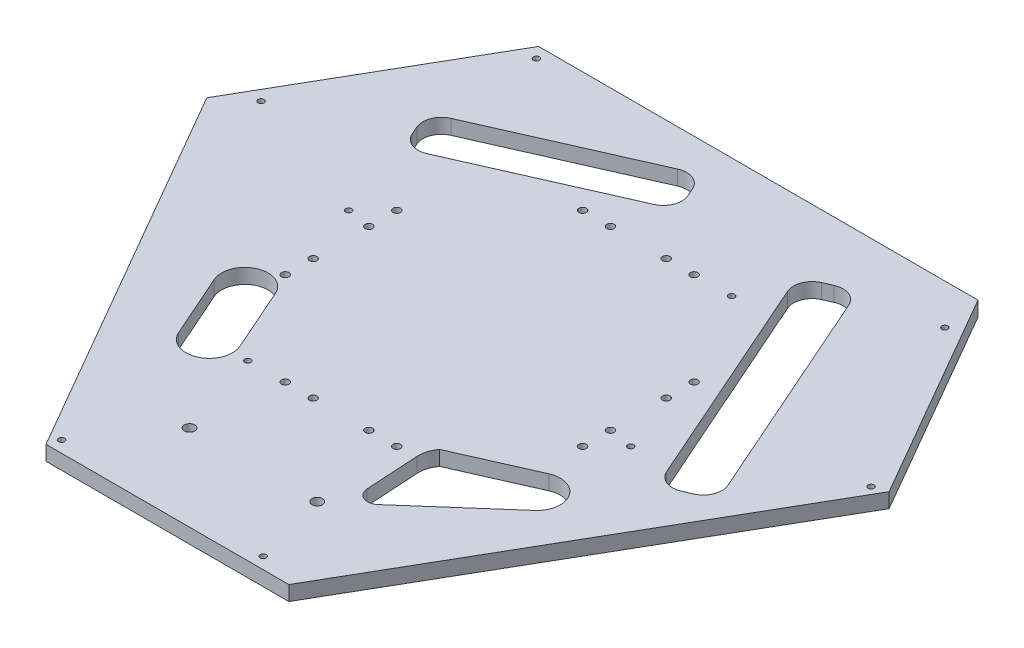
SolidWorks part; units mm, degrees
material "Pin"
ref_plane "Plan de face" through (0, 0, 0) normal (0, 0, 1) x (1, 0, 0)
ref_plane "Plan de dessus" through (0, 0, 0) normal (0, 1, 0) x (1, 0, 0)
ref_plane "Plan de droite" through (0, 0, 0) normal (1, 0, 0) x (0, 0, -1)
sketch "BB_position" plane through (0, 0, 0) normal (0, 1, 0) x (1, 0, 0)
  line L0 (-112.5, 64.9519) -> (112.5, 64.9519) construction
  line L7 (112.5, 64.9519) -> (0, -129.9038) construction
  line L8 (0, -129.9038) -> (-112.5, 64.9519) construction
  circle A0 centre (0, 0) radius 129.9038 construction
  circle A1 centre (-112.5, 64.9519) radius 5 construction
  circle A2 centre (112.5, 64.9519) radius 5 construction
  circle A3 centre (0, -129.9038) radius 5 construction
  dimension "D1" = 225
  dimension "D2" = 10
sketch "BB_Footprint" plane through (0, 0, 0) normal (0, 1, 0) x (1, 0, 0)
  line L0 (-112.5, 64.9519) -> (-130.615, 33.5758) construction
  line L1 (-130.615, 33.5758) -> (-133.9232, 35.4858) construction
  line L2 (-133.9232, 35.4858) -> (-90.5354, 110.6358) construction
  line L3 (97.6932, 98.238) -> (141.0811, 23.088) construction
  line L4 (112.5, 64.9519) -> (94.385, 96.328) construction
  line L5 (94.385, 96.328) -> (97.6932, 98.238) construction
  line L6 (36.23, -133.7238) -> (-50.5457, -133.7238) construction
  line L7 (0, -129.9038) -> (36.23, -129.9038) construction
  line L8 (36.23, -129.9038) -> (36.23, -133.7238) construction
  circle A0 centre (-112.5, 64.9519) radius 5 construction
  circle A1 centre (0, 0) radius 129.9038 construction
  circle A2 centre (-112.5, 64.9519) radius 5 construction
  circle A3 centre (112.5, 64.9519) radius 5 construction
  circle A4 centre (0, -129.9038) radius 5 construction
  point P23 (0, 0)
  dimension "D1" = 3.82
  dimension "D2" = 36.23
  dimension "D3" = 86.7757
  dimension "D4" = 3
sketch "Esquisse3" plane through (0, 0, 0) normal (0, 1, 0) x (1, 0, 0)
  line L0 (-94.5768, 115.6358) -> (94.5768, 115.6358)
  line L1 (-94.5768, 115.6358) -> (-146.8546, 25.088)
  line L2 (-146.8546, 25.088) -> (-52.2778, -138.7238)
  line L3 (-52.2778, -138.7238) -> (52.2778, -138.7238)
  line L4 (52.2778, -138.7238) -> (146.8546, 25.088)
  line L5 (146.8546, 25.088) -> (94.5768, 115.6358)
  line L6 (-133.9232, 35.4858) -> (-90.5354, 110.6358) construction
  point P2 (0, 115.6358)
  point P7 (0, -138.7238)
  dimension "D1" = 5
  dimension "D2" = 4
  dimension "D3" = 5
sketch "TB_boltPattern" plane through (0, 0, 0) normal (0, 1, 0) x (1, 0, 0)
  line L0 (0, 143.3581) -> (0, -141.7362) construction
  line L1 (-23, 57.7) -> (-13, 57.7) construction
  line L2 (-23, 57.7) -> (-23, 43.7) construction
  line L3 (-23, 43.7) -> (-13, 43.7) construction
  line L4 (-13, 57.7) -> (-13, 43.7) construction
  line L5 (-57.7, 23) -> (-43.7, 23) construction
  line L6 (-57.7, 23) -> (-57.7, 13) construction
  line L7 (-57.7, 13) -> (-43.7, 13) construction
  line L8 (-43.7, 23) -> (-43.7, 13) construction
  line L9 (-204.4729, 0) -> (279.6048, 0) construction
  circle A0 centre (-24, 64) radius 1.6 construction
  circle A1 centre (-12, 64) radius 1.6 construction
  circle A2 centre (-64, 24) radius 1.6 construction
  circle A3 centre (-64, 12) radius 1.6 construction
  point P8 (-18, 57.7)
  dimension "D5" = 3.2
  dimension "D10" = 6.3
  dimension "D1" = 12
  dimension "D2" = 12
  dimension "D3" = 40
  dimension "D4" = 40
  dimension "D6" = 14
  dimension "D7" = 10
  dimension "D8" = 1
  dimension "D9" = 6.3
  dimension "D11" = 1
  dimension "D12" = 12
  dimension "D13" = 12
extrude "Plate" add sketch "Esquisse3" against normal blind 6.35
hole_wizard "BBCase_boltPattern" positions "Esquisse6" profile "Esquisse8" hole size "M3" standard "Ansi Metric"
sketch "Esquisse6" plane through (0, 0, 0) normal (0, 1, 0) x (1, 0, 0)
  point P0 (-90.5354, 110.6358)
  point P3 (-133.9232, 35.4858)
sketch "Esquisse8" plane through (-90.5354, 0, -110.6358) normal (1, 0, 0) x (0, 0, 1)
  line L0 (0, 0) -> (0, 7.1311)
  line L1 (0, 7.1311) -> (1.3, 6.35)
  line L2 (1.3, 6.35) -> (1.3, 0)
  line L5 (1.3, 0) -> (0, 0)
  line L10 (0, 7.1311) -> (-1.3, 6.35) construction
  line L11 (0, -6.35) -> (0, 107.95) construction
  dimension "Diamètre du perçage" = 2.6
  dimension "Profondeur du perçage" = 6.35
  dimension "Angle de pointe" = 118
ref_axis "Axe1" through (0, 0, 0) along (0, 1, 0)
pattern_circular "Répétition circulaire1" count 3 over 360 about axis through (0, 0, 0) along (0, 1, 0) of "BBCase_boltPattern"
hole_wizard "Dégagement M32" positions "Esquisse9" profile "Esquisse10" hole size "M3" standard "Ansi Metric"
sketch "Esquisse9" plane through (0, 0, 0) normal (0, 1, 0) x (1, 0, 0)
  point P0 (-24, 64)
  point P3 (-12, 64)
  point P6 (-64, 24)
  point P9 (-64, 12)
sketch "Esquisse10" plane through (-24, 0, -64) normal (1, 0, 0) x (0, 0, 1)
  line L0 (0, 0) -> (0, 7.3114)
  line L1 (0, 7.3114) -> (1.6, 6.35)
  line L2 (1.6, 6.35) -> (1.6, 0)
  line L5 (1.6, 0) -> (0, 0)
  line L10 (0, 7.3114) -> (-1.6, 6.35) construction
  line L11 (0, -6.35) -> (0, 107.95) construction
  dimension "Diamètre du perçage" = 3.2
  dimension "Profondeur du perçage" = 6.35
  dimension "Angle de pointe" = 118
pattern_circular "Répétition circulaire2" count 4 over 360 about axis through (0, 0, 0) along (0, 1, 0) of "Dégagement M32"
sketch "HB_Footprint" plane through (0, 0, 0) normal (0, 1, 0) x (1, 0, 0)
  line L0 (-74.3426, 13.6262) -> (40.0015, 64.1278) construction
  line L1 (40.0015, 64.1278) -> (74.3426, -13.6262) construction
  line L2 (-74.3426, 13.6262) -> (-40.0015, -64.1278) construction
  line L3 (-40.0015, -64.1278) -> (74.3426, -13.6262) construction
  line L8 (-77.8072, 30.1336) -> (-30.1336, -77.8072) construction
  line L9 (-30.1336, -77.8072) -> (77.8072, -30.1336) construction
  line L10 (77.8072, -30.1336) -> (30.1336, 77.8072) construction
  line L11 (-77.8072, 30.1336) -> (30.1336, 77.8072) construction
  line L12 (-23.8368, 53.9704) -> (23.8368, -53.9704) construction
  line L13 (-57.1721, -25.2508) -> (0, 0) construction
  circle A0 centre (-74.3426, 13.6262) radius 1.6 construction
  circle A1 centre (40.0015, 64.1278) radius 1.6 construction
  circle A2 centre (-40.0015, -64.1278) radius 1.6 construction
  circle A3 centre (74.3426, -13.6262) radius 1.6 construction
  point P10 (23.8368, -53.9704)
  point P19 (-17.1706, 38.877)
  dimension "D4" = 3.2
  dimension "D1" = 125
  dimension "D2" = 85
  dimension "D3" = 118
hole_wizard "Dégagement M33" positions "Esquisse11" profile "Esquisse12" hole size "M3" standard "Ansi Metric"
sketch "Esquisse11" plane through (0, 0, 0) normal (0, 1, 0) x (1, 0, 0)
  point P0 (-74.3426, 13.6262)
  point P3 (-40.0015, -64.1278)
  point P6 (74.3426, -13.6262)
  point P9 (40.0015, 64.1278)
sketch "Esquisse12" plane through (-74.3426, 0, -13.6262) normal (1, 0, 0) x (0, 0, 1)
  line L0 (0, 0) -> (0, 7.1311)
  line L1 (0, 7.1311) -> (1.3, 6.35)
  line L2 (1.3, 6.35) -> (1.3, 0)
  line L5 (1.3, 0) -> (0, 0)
  line L10 (0, 7.1311) -> (-1.3, 6.35) construction
  line L11 (0, -6.35) -> (0, 107.95) construction
  dimension "Diamètre du perçage" = 2.6
  dimension "Profondeur du perçage" = 6.35
  dimension "Angle de pointe" = 118
sketch "Esquisse13" plane through (0, 0, 0) normal (0, 1, 0) x (1, 0, 0)
  line L0 (113.0252, -14.5791) -> (94.7302, -22.6594)
  line L1 (94.7302, -22.6594) -> (47.0566, 85.2815)
  line L2 (47.0566, 85.2815) -> (65.3516, 93.3617)
  line L3 (65.3516, 93.3617) -> (113.0252, -14.5791)
  line L5 (-77.8072, 30.1336) -> (30.1336, 77.8072) construction
  line L7 (40.0015, 64.1278) -> (74.3426, -13.6262) construction
  line L13 (-30.1336, -77.8072) -> (77.8072, -30.1336) construction
  line L14 (-11.64, 103.085) -> (-93.9678, 66.7238)
  line L15 (-93.9678, 66.7238) -> (-85.8875, 48.4287)
  line L16 (-85.8875, 48.4287) -> (-3.5597, 84.7899)
  line L17 (-3.5597, 84.7899) -> (-11.64, 103.085)
  line L18 (-77.8072, 30.1336) -> (-30.1336, -77.8072) construction
  dimension "D1" = 15
  dimension "D2" = 20
  dimension "D5" = 20
  dimension "D6" = 90
  dimension "D7" = 20
extrude "Enlèv. mat.-Extru.1" cut sketch "Esquisse13" against normal up to surface (6.35 mm away) up to face at (-40.0015, -6.35, 65.4278)
sketch "Esquisse15" plane through (0, 0, 0) normal (0, 1, 0) x (1, 0, 0)
  line L0 (-27.48, -101.7238) -> (27.48, -101.7238) construction
  line L1 (0, 200143.3581) -> (0, -200141.7362) construction
  line L2 (-52.2778, -138.7238) -> (52.2778, -138.7238) construction
  circle A0 centre (-27.48, -101.7238) radius 3.5746 construction
  circle A1 centre (27.48, -101.7238) radius 3.5746 construction
  point P4 (0, -101.7238)
  dimension "D1" = 54.96
  dimension "D2" = 37
hole_wizard "Dégagement M51" positions "Esquisse16" profile "Esquisse17" hole size "M5" standard "Ansi Metric"
sketch "Esquisse16" plane through (0, 0, 0) normal (0, 1, 0) x (1, 0, 0)
  point P0 (-27.48, -101.7238)
  point P3 (27.48, -101.7238)
sketch "Esquisse17" plane through (-27.48, 0, 101.7238) normal (1, 0, 0) x (0, 0, 1)
  line L0 (0, 0) -> (0, 7.714)
  line L1 (0, 7.714) -> (2.27, 6.35)
  line L2 (2.27, 6.35) -> (2.27, 0)
  line L5 (2.27, 0) -> (0, 0)
  line L10 (0, 7.714) -> (-2.27, 6.35) construction
  line L11 (0, -6.35) -> (0, 107.95) construction
  dimension "Diamètre du perçage" = 4.54
  dimension "Profondeur du perçage" = 6.35
  dimension "Angle de pointe" = 118
sketch "Esquisse18" plane through (0, 0, 0) normal (0, 1, 0) x (1, 0, 0)
  line L0 (71.0075, -50.6279) -> (43.5649, -62.7483) construction
  line L2 (66.9674, -41.4803) -> (34.336, -55.8925)
  line L3 (-30.1336, -77.8072) -> (77.8072, -30.1336) construction
  line L4 (23.8368, -53.9704) -> (77.8072, -30.1336) construction
  line L5 (50.822, -42.052) -> (57.2862, -56.6881) construction
  line L6 (-68.3683, -37.0282) -> (-56.2479, -64.4708) construction
  line L7 (-59.2207, -32.9881) -> (-47.1003, -60.4307)
  line L8 (-77.5158, -41.0684) -> (-65.3954, -68.511)
  line L9 (-74.3426, 13.6262) -> (-40.0015, -64.1278) construction
  line L10 (-57.1721, -25.2508) -> (-40.0015, -64.1278) construction
  line L11 (-48.5868, -44.6893) -> (-62.3081, -50.7495) construction
  line L12 (32.0883, -63.4284) -> (33.4385, -86.2128)
  line L13 (41.7305, -89.6726) -> (77.6091, -58.1391)
  arc A0 (77.6091, -58.1391) -> (66.9674, -41.4803) centre (71.0075, -50.6279) ccw
  arc A1 (34.336, -55.8925) -> (32.0883, -63.4284) centre (43.5649, -62.7483) ccw
  arc A2 (-59.2207, -32.9881) -> (-77.5158, -41.0684) centre (-68.3683, -37.0282) ccw
  arc A3 (-65.3954, -68.511) -> (-47.1003, -60.4307) centre (-56.2479, -64.4708) ccw
  arc A4 (33.4385, -86.2128) -> (41.7305, -89.6726) centre (38.4297, -85.917) ccw
  point P2 (57.2862, -56.6881)
  point P16 (-62.3081, -50.7495)
  point P35 (34.0438, -96.4284)
  dimension "D4" = 15
  dimension "D6" = 10
  dimension "D1" = 10
  dimension "D11" = 5
  dimension "D2" = 6
  dimension "D3" = 30
  dimension "D5" = 30
  dimension "D7" = 35
  dimension "D8" = 58
  dimension "D9" = 10
  dimension "D10" = 33
extrude "Enlèv. mat.-Extru.3" cut sketch "Esquisse18" against normal up to surface (6.35 mm away) up to face at (-27.48, -6.35, 103.9938)
fillet "Congé1" radius 8 8 edges at (47.0566, -3.175, -85.2815) (65.3516, -3.175, -93.3617) (113.0252, -3.175, 14.5791) (94.7302, -3.175, 22.6594) (-11.64, -3.175, -103.085) (-3.5597, -3.175, -84.7899) (-85.8875, -3.175, -48.4287) (-93.9678, -3.175, -66.7238)
